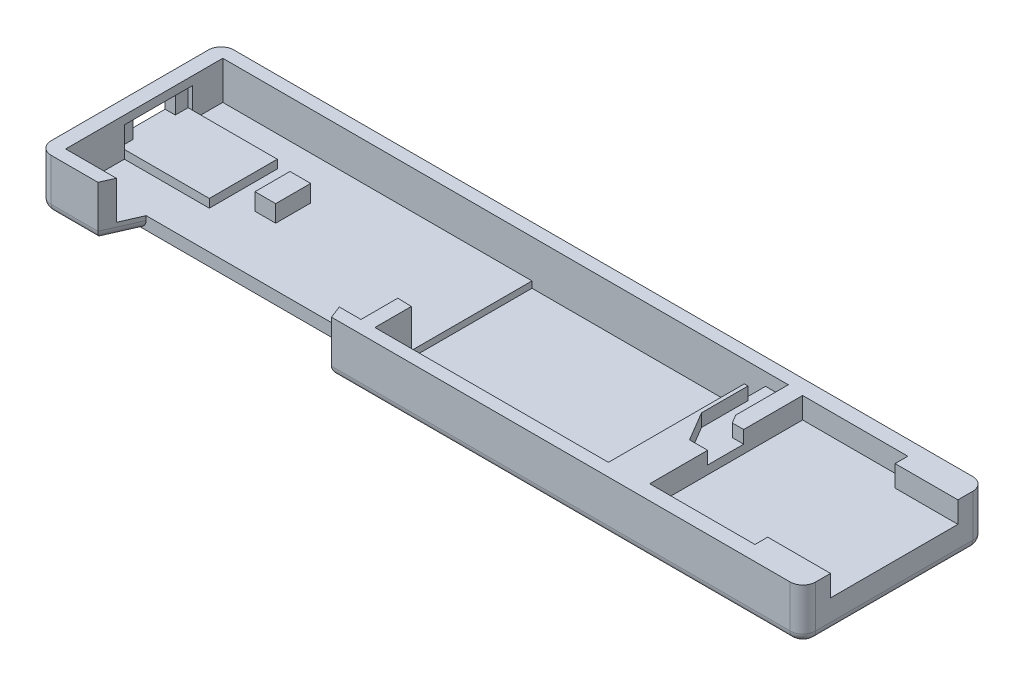
SolidWorks part; units mm, degrees
ref_plane "前视基准面" through (0, 0, 0) normal (0, 0, 1) x (1, 0, 0)
ref_plane "上视基准面" through (0, 0, 0) normal (0, 1, 0) x (1, 0, 0)
ref_plane "右视基准面" through (0, 0, 0) normal (1, 0, 0) x (0, 0, -1)
sketch "草图3" plane through (0, 0, 0) normal (0, 1, 0) x (1, 0, 0)
  line L1 (-39.9314, 29.2531) -> (140.0686, 29.2531)
  line L2 (-39.9314, 29.2531) -> (-39.9314, -13.7469)
  line L3 (-39.9314, -13.7469) -> (140.0686, -13.7469)
  line L4 (140.0686, 29.2531) -> (140.0686, -13.7469)
extrude "凸台-拉伸1" add sketch "草图3" along normal blind 12
sketch "草图4" plane through (0, 0, 0) normal (0, 1, 0) x (1, 0, 0)
  line L0 (-22.4696, -5.8589) -> (26.0023, -5.8589)
  line L1 (-39.9314, -13.7469) -> (140.0686, -13.7469) construction
  line L2 (-25.9314, -13.7469) -> (29.0686, -13.7469)
  line L5 (-25.9314, -13.7469) -> (-22.4696, -5.8589)
  line L6 (29.0686, -13.7469) -> (26.0023, -5.8589)
  point P11 (-22.4696, -5.8589)
  point P12 (26.0023, -5.8589)
extrude "切除-拉伸1" cut sketch "草图4" along normal blind 52
sketch "草图5" plane through (0, 12, 0) normal (0, 1, 0) x (1, 0, 0)
  line L6 (140.0686, -13.7469) -> (140.0686, 29.2531) construction
  line L7 (140.0686, 7.7531) -> (140.0686, 22.7531)
  line L8 (140.0686, 7.7531) -> (140.0686, -7.2469)
  line L9 (140.0686, 22.7531) -> (125.2765, 22.7531)
  line L10 (125.2765, 22.7531) -> (125.2765, -7.2469)
  line L11 (125.2765, -7.2469) -> (140.0686, -7.2469)
  point P0 (140.0686, 7.7531)
extrude "切除-拉伸2" cut sketch "草图5" against normal blind 5
sketch "草图7" plane through (0, 12, 0) normal (0, 1, 0) x (1, 0, 0)
  line L0 (125.2765, 22.7531) -> (125.2765, -7.2469) construction
  line L1 (125.2765, 7.7531) -> (125.2765, 25.7531)
  line L2 (125.2765, 7.7531) -> (125.2765, -10.2469)
  line L3 (125.2765, -10.2469) -> (100.5008, -10.2469)
  line L4 (100.5008, -10.2469) -> (100.5008, 25.7531)
  line L5 (100.5008, 25.7531) -> (125.2765, 25.7531)
  point P0 (125.2765, 7.7531)
extrude "切除-拉伸3" cut sketch "草图7" against normal blind 5
sketch "草图8" plane through (0, 12, 0) normal (0, 1, 0) x (1, 0, 0)
  line L1 (36.2763, 26.2531) -> (91.2763, 26.2531)
  line L2 (36.2763, 26.2531) -> (36.2763, -10.7469)
  line L3 (36.2763, -10.7469) -> (91.2763, -10.7469)
  line L4 (91.2763, 26.2531) -> (91.2763, -10.7469)
  line L6 (140.0686, 29.2531) -> (-39.9314, 29.2531) construction
  line L7 (29.0686, -13.7469) -> (140.0686, -13.7469) construction
  dimension "D1" = 3
  dimension "D2" = 3
extrude "切除-拉伸4" cut sketch "草图8" against normal blind 10.5
sketch "草图9" plane through (0, 12, 0) normal (0, 1, 0) x (1, 0, 0)
  line L0 (91.2763, -10.7469) -> (91.2763, 26.2531) construction
  line L1 (91.2763, 26.2531) -> (96.6358, 26.2531)
  line L2 (91.2763, 26.2531) -> (91.2763, 21.2551)
  line L4 (96.6358, 26.2531) -> (96.6358, 22.1306)
  line L5 (100.5008, 25.7531) -> (100.5008, -10.2469) construction
  line L7 (92.1327, 21.2551) -> (92.1327, 10.3104)
  line L12 (96.2367, 3.394) -> (100.5008, 3.394)
  line L13 (100.5008, 11.8772) -> (100.5008, 3.394)
  line L14 (92.1327, 10.3104) -> (96.2367, 3.394)
  line L15 (96.6358, 13.8621) -> (97.8136, 11.8772)
  line L17 (97.8136, 11.8772) -> (100.5008, 11.8772)
  line L19 (96.6358, 13.8621) -> (96.6358, 22.1306)
  line L20 (92.1327, 21.2551) -> (91.2763, 21.2551)
extrude "切除-拉伸5" cut sketch "草图9" against normal blind 3
sketch "草图10" plane through (0, 12, 0) normal (0, 1, 0) x (1, 0, 0)
  line L4 (-29.1302, -10.7469) -> (32.9986, -10.7469)
  line L5 (-29.1302, -10.7469) -> (-29.1302, -2.0631)
  line L6 (-29.1302, -2.0631) -> (32.9986, -2.0631)
  line L7 (32.9986, -10.7469) -> (32.9986, -2.0631)
extrude "切除-拉伸6" cut sketch "草图10" against normal blind 8
sketch "草图11" plane through (0, 12, 0) normal (0, 1, 0) x (1, 0, 0)
  line L0 (32.9986, -10.7469) -> (-36.5397, -10.7469)
  line L1 (36.2763, 26.2531) -> (36.2763, -10.7469) construction
  line L5 (-36.5397, 26.2531) -> (-36.5397, -10.7469)
  line L9 (36.2763, 26.2531) -> (36.2763, -2.1672)
  line L10 (-36.5397, 26.2531) -> (36.2763, 26.2531)
  line L11 (32.9986, -10.7469) -> (32.9986, -2.0631)
  line L12 (32.9986, -10.7469) -> (32.9986, -2.0631) construction
  line L13 (32.9986, -2.0631) -> (36.2763, -2.1672)
extrude "切除-拉伸8" cut sketch "草图11" against normal blind 9
fillet "圆角2" radius 2 7 edges at (140.0686, 0, -7.7531) (84.5686, 0, 13.7469) (27.5354, 0, 9.8029) (-24.2005, 0, 9.8029) (-32.9314, 0, 13.7469) (-39.9314, 0, -7.7531) (50.0686, 0, -29.2531)
fillet "圆角3" radius 3 8 edges at (-39.3456, 0.5858, -28.6673) (-39.3456, 0.5858, 13.1611) (139.4828, 0.5858, 13.1611) (139.4828, 0.5858, -28.6673) (140.0686, 7, -29.2531) (140.0686, 7, 13.7469) (-39.9314, 7, 13.7469) (-39.9314, 7, -29.2531)
sketch "草图12" plane through (0, 3, 0) normal (0, 1, 0) x (1, 0, 0)
  line L0 (-36.5397, 26.2531) -> (-36.5397, -10.7469) construction
  line L1 (-36.5397, 19.0821) -> (-16.5397, 19.0821)
  line L2 (-36.5397, 19.0821) -> (-36.5397, 3.0821)
  line L3 (-36.5397, 3.0821) -> (-16.5397, 3.0821)
  line L4 (-16.5397, 19.0821) -> (-16.5397, 3.0821)
extrude "凸台-拉伸2" add sketch "草图12" along normal blind 2
sketch "草图13" plane through (-36.5397, 0, 0) normal (1, 0, 0) x (0, 0, -1)
  line L1 (3.0821, 5) -> (19.0821, 5)
  line L2 (3.0821, 5) -> (3.0821, 10)
  line L3 (3.0821, 10) -> (19.0821, 10)
  line L4 (19.0821, 5) -> (19.0821, 10)
extrude "切除-拉伸9" cut sketch "草图13" against normal blind 1
sketch "草图14" plane through (-37.5397, 0, 0) normal (1, 0, 0) x (0, 0, -1)
  line L1 (3.0821, 5) -> (19.0821, 5) construction
  line L4 (16.0821, 5) -> (6.0821, 5)
  line L5 (16.0821, 5) -> (16.0821, 9.5)
  line L6 (16.0821, 9.5) -> (6.0821, 9.5)
  line L7 (6.0821, 5) -> (6.0821, 9.5)
extrude "切除-拉伸10" cut sketch "草图14" against normal blind 11
sketch "草图15" plane through (0, 5, 0) normal (0, 1, 0) x (1, 0, 0)
  line L2 (-10.5397, 16.0821) -> (-5.6617, 16.0821)
  line L3 (-10.5397, 16.0821) -> (-10.5397, 7.8336)
  line L4 (-10.5397, 7.8336) -> (-5.6617, 7.8336)
  line L5 (-5.6617, 16.0821) -> (-5.6617, 7.8336)
extrude "凸台-拉伸3" add sketch "草图15" along normal blind 2 and the other way blind 3
